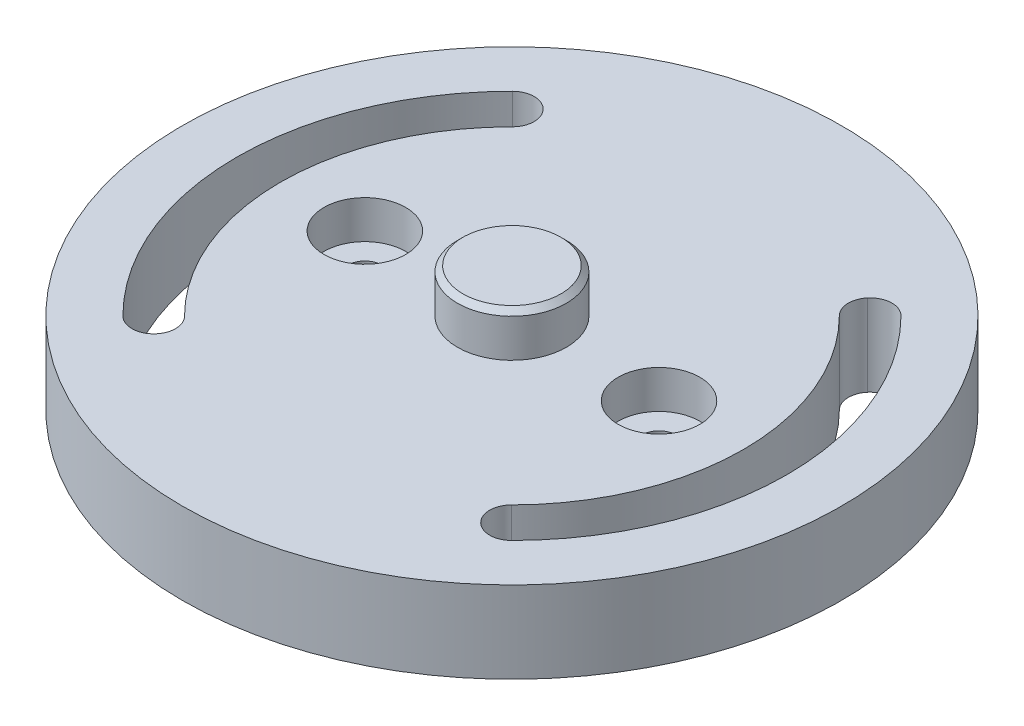
SolidWorks part; units mm, degrees
material "Alumina"
ref_plane "Front Plane" through (0, 0, 0) normal (0, 0, 1) x (1, 0, 0)
ref_plane "Top Plane" through (0, 0, 0) normal (0, 1, 0) x (1, 0, 0)
ref_plane "Right Plane" through (0, 0, 0) normal (1, 0, 0) x (0, 0, -1)
sketch "Sketch1" plane through (0, 0, 0) normal (0, 1, 0) x (1, 0, 0)
  line L0 (0, 0) -> (50.5, 0) construction
  line L1 (27.3185, 32.5569) -> (32.4608, 38.6852)
  line L2 (27.3185, -32.5569) -> (32.4608, -38.6852)
  line L3 (0, -50.5) -> (0, 50.5) construction
  line L4 (-27.3185, -32.5569) -> (-32.4608, -38.6852)
  line L5 (-27.3185, 32.5569) -> (-32.4608, 38.6852)
  circle A0 centre (0, 0) radius 42.5
  circle A1 centre (0, 0) radius 50.5
  circle A2 centre (0, 0) radius 60.5
  dimension "D1" = 85
  dimension "D2" = 101
  dimension "D3" = 50
  dimension "D4" = 50
  dimension "D5" = 8
  dimension "D6" = 50.5
  dimension "D9" = 10
extrude "Boss-Extrude1" add sketch "Sketch1" along normal blind 15 contours A0 | L1 A1 L5 A0 | A2 A1 | L4 A1 L2 A0 region at (0, 0, -42.9193) region at (0, 0, 0) region at (0, 0, 42.9193) region at (-58.7888, 0, 0)
sketch "Sketch2" plane through (0, 15, 0) normal (0, 1, 0) x (1, 0, 0)
  line L0 (0, 0) -> (-27, 0) construction
  line L1 (0, 0) -> (27, 0) construction
  circle A0 centre (-27, 0) radius 7.5
  circle A1 centre (27, 0) radius 7.5
  dimension "D3" = 15
  dimension "D4" = 15
  dimension "D1" = 27
  dimension "D2" = 27
extrude "Cut-Extrude1" cut sketch "Sketch2" against normal blind 7
sketch "Sketch3" plane through (0, 15, 0) normal (0, 1, 0) x (1, 0, 0)
  circle A0 centre (-27, 0) radius 3.15
  circle A1 centre (27, 0) radius 3.15
  dimension "D1" = 6.3
  dimension "D2" = 6.3
extrude "Cut-Extrude2" cut sketch "Sketch3" against normal up to surface (15 mm away) up to face at (-38.1948, 0, 0)
fillet "Fillet1" radius 4 8 edges at (32.4608, 7.5, 38.6852) (27.3185, 7.5, 32.5569) (-27.3185, 7.5, 32.5569) (-32.4608, 7.5, 38.6852) (32.4608, 7.5, -38.6852) (27.3185, 7.5, -32.5569) (-27.3185, 7.5, -32.5569) (-32.4608, 7.5, -38.6852)
sketch "Sketch4" plane through (0, 15, 0) normal (0, 1, 0) x (1, 0, 0)
  circle A0 centre (0, 0) radius 10
  dimension "D1" = 20
extrude "Boss-Extrude2" add sketch "Sketch4" along normal blind 8
chamfer "Chamfer1" distance 1 angle 45 1 edges at (0, 23, 10)
